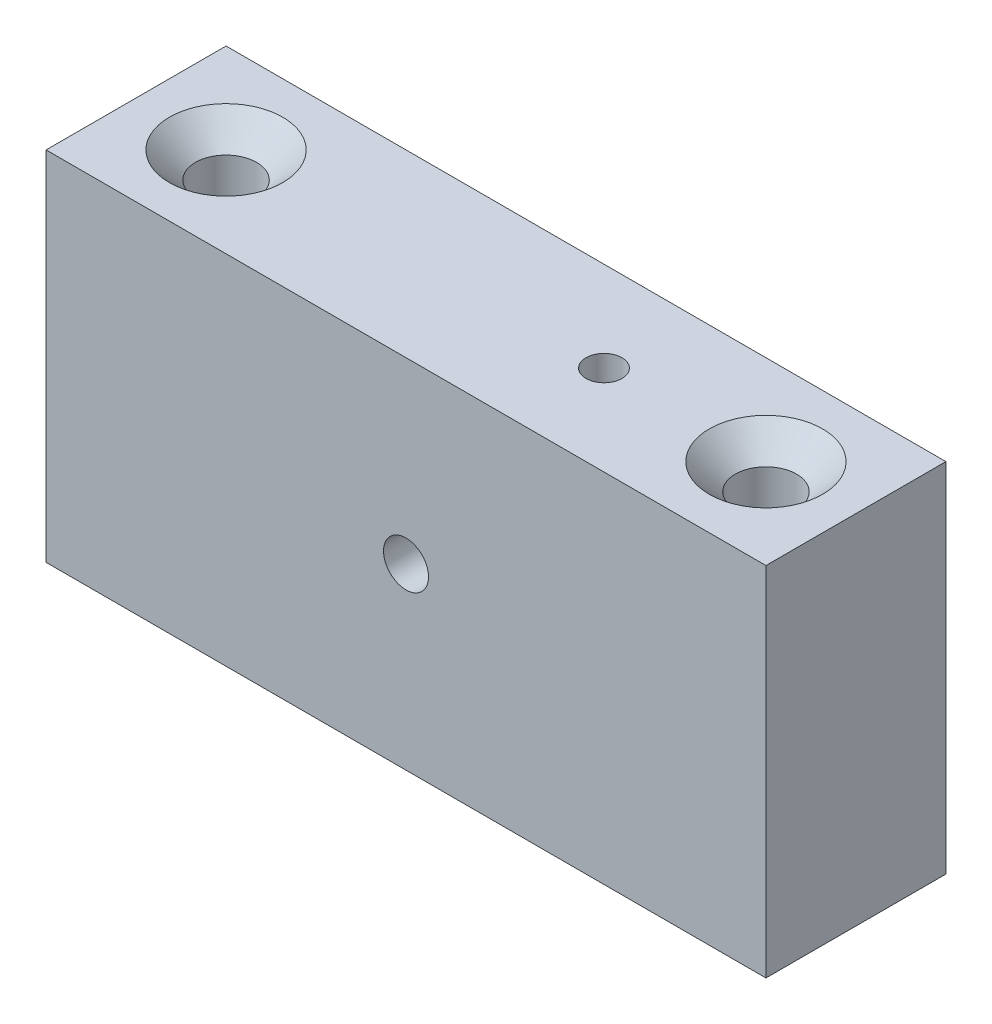
SolidWorks part; units mm, degrees
material "Copper"
ref_plane "Front Plane" through (0, 0, 0) normal (0, 0, 1) x (1, 0, 0)
ref_plane "Top Plane" through (0, 0, 0) normal (0, 1, 0) x (1, 0, 0)
ref_plane "Right Plane" through (0, 0, 0) normal (1, 0, 0) x (0, 0, -1)
sketch "Sketch1" plane through (0, 0, 0) normal (0, 1, 0) x (1, 0, 0)
  line L0 (0, 5) -> (40, 5) construction
  line L1 (0, 0) -> (40, 0)
  line L2 (0, 0) -> (0, 10)
  line L3 (0, 10) -> (40, 10)
  line L4 (40, 0) -> (40, 10)
  line L5 (5, 5) -> (5, 10) construction
  line L6 (35, 10) -> (35, 5) construction
  dimension "D1" = 5
  dimension "D2" = 5
  dimension "D3" = 5
  dimension "D4" = 5
  dimension "D5" = 40
extrude "Boss-Extrude1" add sketch "Sketch1" along normal blind 19.85
sketch "Sketch2" plane through (0, 19.85, 0) normal (0, 1, 0) x (1, 0, 0)
  point P0 (35, 5)
  point P2 (5, 5)
hole_wizard "CSK for M3 Flat Head Machine Screw1" positions "3DSketch1" profile "Sketch3" countersink size "M3" standard "ANSI Metric" end condition through all
sketch3d "3DSketch1"
  point P0 (5, 19.85, -5)
  point P3 (35, 19.85, -5)
sketch "Sketch3" plane through (5, 19.85, -5) normal (1, 0, 0) x (0, 0, 1)
  line L0 (0, 0) -> (0, 19.85)
  line L1 (0, 19.85) -> (1.7, 19.85)
  line L2 (1.7, 19.85) -> (1.7, 1.45)
  line L3 (1.7, 1.45) -> (3.15, 0)
  line L5 (3.15, 0) -> (0, 0)
  line L6 (-1.7, 1.45) -> (-3.15, 0) construction
  line L11 (0, -6.35) -> (0, 107.95) construction
  dimension "Thru Hole Dia." = 3.4
  dimension "Thru Hole Depth" = 19.85
  dimension "Near C'Sink Dia." = 6.3
  dimension "Near C'Sink Angle" = 90
ref_plane "Plane1" through (20, 0, 0) normal (-1, 0, 0) x (0, 0, 1)
sketch "Sketch4" plane through (0, 0, -10) normal (0, 0, -1) x (-1, 0, 0)
  line L0 (-40, 9.925) -> (0, 9.925) construction
  line L1 (-40, 19.85) -> (-40, 0) construction
  line L2 (0, 19.85) -> (0, 0) construction
hole_wizard "M3x0.5 Tapped Hole1" positions "3DSketch2" profile "Sketch5" tap size "M3x0.5" standard "ANSI Metric" end condition through all
sketch3d "3DSketch2"
  line L0 (40, 9.925, -10) -> (0, 9.925, -10) construction
  point P0 (20, 9.925, -10)
  point P4 (20, 9.925, -10)
cosmetic thread "Hole Thread2" parameters "D2"=3
sketch "Sketch5" plane through (20, 9.925, -10) normal (1, 0, 0) x (0, 1, 0)
  line L0 (0, 0) -> (0, 10)
  line L1 (0, 10) -> (1.25, 10)
  line L2 (1.25, 10) -> (1.25, 0)
  line L5 (1.25, 0) -> (0, 0)
  line L11 (0, -6.35) -> (0, 107.95) construction
  dimension "Thru Tap Drill Dia." = 2.5
  dimension "Thru Tap Drill Depth" = 10
sketch "Sketch6" plane through (0, 19.85, 0) normal (0, 1, 0) x (1, 0, 0)
  line L0 (40, 5) -> (26, 5) construction
  line L1 (40, 0) -> (40, 10) construction
  dimension "D2" = 14
hole_wizard "Ø2.0mm Dowel Hole1" positions "3DSketch3" profile "Sketch7" hole size "Ø2.0" standard "ANSI Metric" end condition through all
sketch3d "3DSketch3"
  point P0 (26, 19.85, -5)
sketch "Sketch7" plane through (26, 19.85, -5) normal (1, 0, 0) x (0, 0, 1)
  line L0 (0, 0) -> (0, 19.85)
  line L1 (0, 19.85) -> (1, 19.85)
  line L2 (1, 19.85) -> (1, 0)
  line L5 (1, 0) -> (0, 0)
  line L11 (0, -6.35) -> (0, 107.95) construction
  dimension "Thru Hole Dia." = 2
  dimension "Thru Hole Depth" = 19.85
equation "\"D2@Sketch1\"=\"D1@Sketch1\""
equation "\"D3@Sketch1\"=\"D1@Sketch1\""
